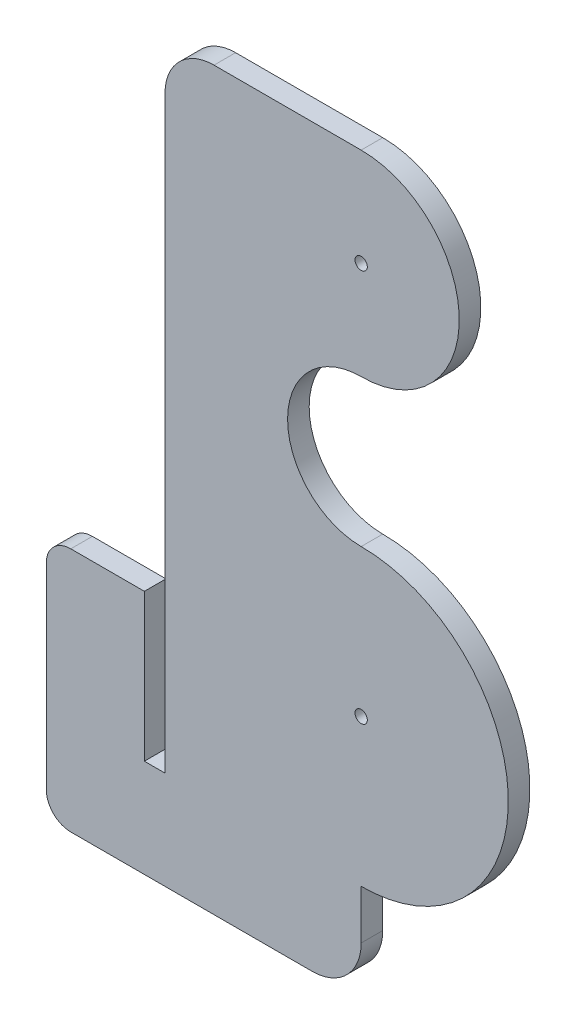
SolidWorks part; units mm, degrees
ref_plane "Front Plane" through (0, 0, 0) normal (0, 0, 1) x (1, 0, 0)
ref_plane "Top Plane" through (0, 0, 0) normal (0, 1, 0) x (1, 0, 0)
ref_plane "Right Plane" through (0, 0, 0) normal (1, 0, 0) x (0, 0, -1)
sketch "Sketch1" plane through (0, 0, 0) normal (0, 0, 1) x (1, 0, 0)
  line L0 (-21.5871, 13.2698) -> (-8.8871, 13.2698)
  line L2 (-21.5871, -18.4802) -> (-21.5871, 13.2698)
  line L4 (19.1799, -18.4802) -> (-21.5871, -18.4802)
  line L5 (-6.2201, 32.313) -> (-6.2201, 76.7698)
  line L6 (-6.2201, 76.7698) -> (19.1799, 76.7698)
  line L8 (-8.8871, 13.2698) -> (-8.8871, -5.7802)
  line L9 (-8.8871, -5.7802) -> (-6.2201, -5.7802)
  line L10 (-6.2201, 32.313) -> (-6.2201, -5.7802)
  line L16 (19.1799, -5.7802) -> (19.1799, -18.4802)
  arc A0 (19.1799, -5.7802) -> (19.1799, 32.3198) centre (19.1799, 13.2698) ccw
  circle A2 centre (19.1799, 13.2698) radius 0.7937
  arc A6 (19.1799, 76.7698) -> (19.1799, 51.3698) centre (19.1799, 64.0698) cw
  circle A7 centre (19.1799, 64.0698) radius 0.7937
  arc A8 (19.1799, 32.3198) -> (19.1799, 51.3698) centre (19.1799, 41.8448) cw
  point P0 (0, 0)
  point P6 (19.1799, 51.3698)
  point P24 (19.1799, 13.2698)
  dimension "D17" = 12.7
  dimension "D10" = 19.05
  dimension "D3" = 2.667
  dimension "D4" = 12.7
  dimension "D8" = 12.7
  dimension "D9" = 25.4
  dimension "D11" = 12.7
  dimension "D12" = 19.05
  dimension "D15" = 25.4
  dimension "D16" = 19.05
extrude "Boss-Extrude1" add sketch "Sketch1" along normal blind 2.794
fillet "Fillet1" radius 6.35 2 edges at (19.1799, -18.4802, 1.397) (-6.2201, 76.7698, 1.397)
fillet "Fillet2" radius 3.175 2 edges at (-21.5871, -18.4802, 1.397) (-21.5871, 13.2698, 1.397)
